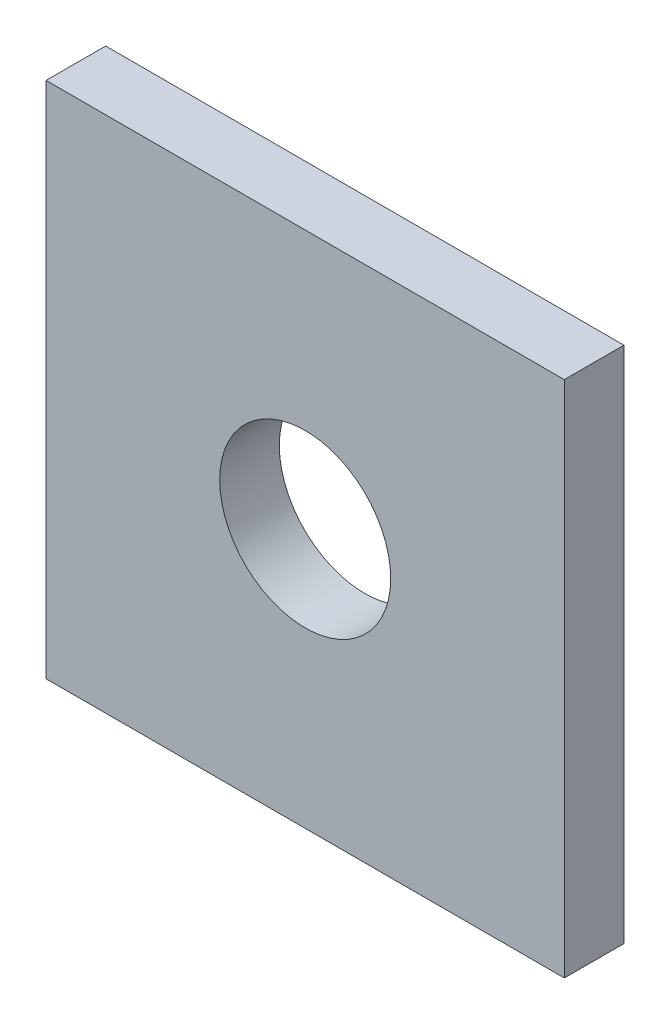
SolidWorks part; units mm, degrees
ref_plane "Front Plane" through (0, 0, 0) normal (0, 0, 1) x (1, 0, 0)
ref_plane "Top Plane" through (0, 0, 0) normal (0, 1, 0) x (1, 0, 0)
ref_plane "Right Plane" through (0, 0, 0) normal (1, 0, 0) x (0, 0, -1)
sketch "BodySke" plane through (0, 0, 0) normal (0, 0, 1) x (1, 0, 0)
  line L0 (0, 0) -> (0, 20) construction
  line L1 (-10, 0) -> (10, 0)
  line L2 (10, 0) -> (10, 20)
  line L3 (10, 20) -> (-10, 20)
  line L4 (-10, 20) -> (-10, 0)
  line L5 (-10, 10) -> (10, 10) construction
  circle A0 centre (0, 10) radius 3.3
  dimension "Inner_dia" = 6.6
  dimension "Side_Length" = 20
extrude "BaseBody" add sketch "BodySke" along normal blind 2.3
